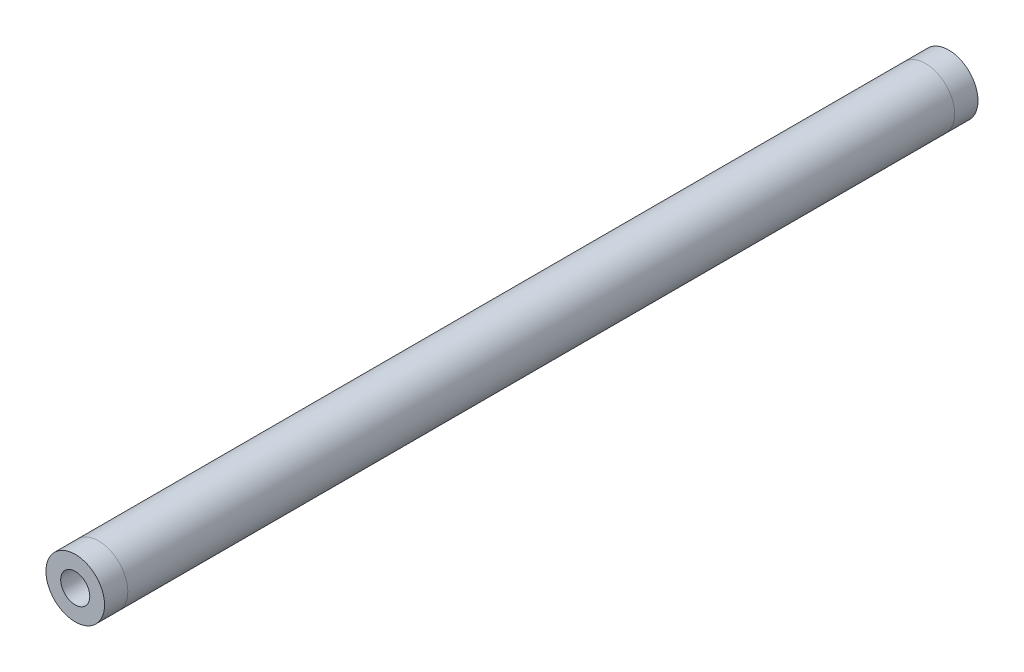
SolidWorks part; units mm, degrees
material "AISI 4130 Steel, annealed at 865C"
ref_plane "Front Plane" through (0, 0, 0) normal (0, 0, 1) x (1, 0, 0)
ref_plane "Top Plane" through (0, 0, 0) normal (0, 1, 0) x (1, 0, 0)
ref_plane "Right Plane" through (0, 0, 0) normal (1, 0, 0) x (0, 0, -1)
sketch "Axis" plane through (0, 0, 0) normal (1, 0, 0) x (0, 0, -1)
  line L0 (0, 0) -> (238.5132, 0) construction
  line L1 (238.5132, 0) -> (232.1632, 0)
  line L2 (238.5132, 0) -> (273.4382, 0) construction
  line L3 (0, 0) -> (-34.925, 0) construction
  point P4 (0, 0)
  point P5 (238.5132, 0)
  point P6 (232.1632, 0)
  point P8 (273.4382, 0)
  dimension "D1" = 6.35
  dimension "D2" = 34.925
  dimension "D3" = 34.925
sketch "Sketch1" plane through (0, 0, 0) normal (0, 0, 1) x (1, 0, 0)
  circle A0 centre (0, 0) radius 8.001
  circle A1 centre (0, 0) radius 6.477
  circle A2 centre (0, 0) radius 3.9688
  dimension "D1" = 16.002
  dimension "D2" = 1.524
  dimension "D3" = 7.9375
extrude "Threaded insert 1-1" add sketch "Sketch1" against normal blind 6.35 contours A0 A1 | A1 A2 region at (-7.7747, 0, 0) region at (-6.2938, 0, 0)
extrude "Threaded insert 1-2" add sketch "Sketch1<3>" against normal blind 9.525 from surface contours A1 A2 region at (-6.2938, 0, 0) starting at face at (8.001, 0, -6.35)
sketch "Sketch1<3>" plane through (0, 0, 0) normal (0, 0, 1) x (1, 0, 0) same geometry as "Sketch1"
extrude "Tube extrude" add sketch "Sketch1<4>" against normal up to vertex (232.1632 mm away) from surface separate body contours A0 A1 region at (-7.7747, 0, 0) up to point (0, 0, -232.1632) starting at face at (6.477, 0, -6.35)
sketch "Sketch1<4>" plane through (0, 0, 0) normal (0, 0, 1) x (1, 0, 0) same geometry as "Sketch1"
extrude "Threaded insert 2-1" add sketch "Sketch1<6>" along normal blind 9.525 from surface separate body contours A1 A2 region at (-6.2938, 0, 0) starting at face at (6.477, 0, -232.1632)
sketch "Sketch1<6>" plane through (0, 0, 0) normal (0, 0, 1) x (1, 0, 0) same geometry as "Sketch1"
extrude "Threaded insert 2-2" add sketch "Sketch1<9>" against normal blind 6.35 from surface separate body contours A1 A2 | A0 A1 region at (-7.7747, 0, 0) region at (-6.2938, 0, 0) starting at face at (6.477, 0, -232.1632)
sketch "Sketch1<9>" plane through (0, 0, 0) normal (0, 0, 1) x (1, 0, 0) same geometry as "Sketch1"
combine bodies "Combine1" operation type add bodies to combine 106 104
equation "\"Threaded insert outer thickness\"= .25"
equation "\"D1@Threaded insert 1-1\"=\"Threaded insert outer thickness\""
equation "\"D1@Threaded insert 2-2\"=\"Threaded insert outer thickness\""
equation "\"D1@Axis\" = \"Threaded insert outer thickness\""
